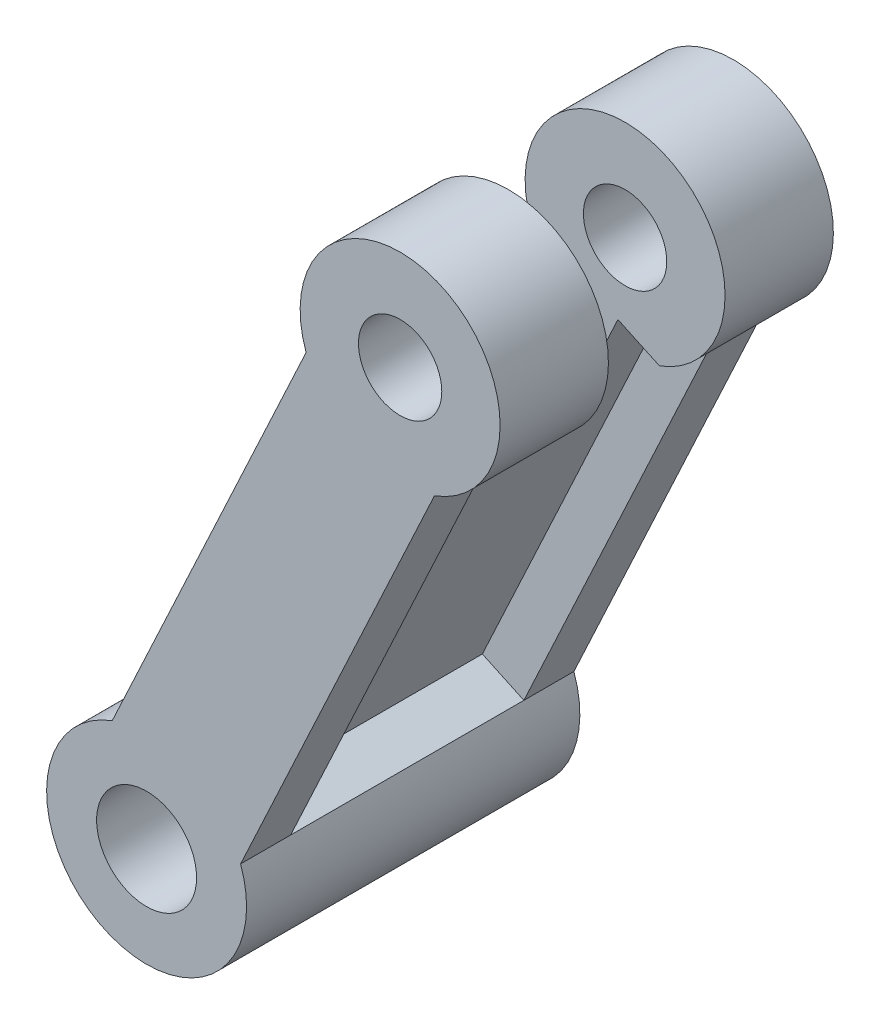
SolidWorks part; units mm, degrees
note: '?' marks a value the reader was unsure of.
material "Custom Plastic"
ref_plane "Piano frontale" through (0, 0, 0) normal (0, 0, 1) x (1, 0, 0)
ref_plane "Piano superiore" through (0, 0, 0) normal (0, 1, 0) x (1, 0, 0)
ref_plane "Piano destro" through (0, 0, 0) normal (1, 0, 0) x (0, 0, -1)
sketch "Sketch1" plane through (0, 0, 0) normal (0, 0, 1) x (1, 0, 0)
  line L0 (0, 0) -> (152.1426, 326.2708) construction
  line L1 (0, 0) -> (129.1028, 0) construction
  line L2 (95.7255, 305.8475) -> (-20.6191, 56.3458)
  line L3 (172.7616, 269.925) -> (56.4171, 20.4233)
  circle A0 centre (0, 0) radius 60
  circle A1 centre (152.1426, 326.2708) radius 60
  dimension "D1" = 120
  dimension "D2" = 120
  dimension "D3" = 65
  dimension "D4" = 360
  dimension "D5" = 42.5
extrude "Boss-Extrude1" add sketch "Sketch1" along normal mid plane 200 contours A1 L2 A0 L3 | A1 | A0
sketch "Sketch2" plane through (0, 0, 0) normal (0, 0, 1) x (1, 0, 0)
  circle A0 centre (0, 0) radius 30
  circle A1 centre (152.1426, 326.2708) radius 25
  dimension "D1" = 60
  dimension "D2" = 50
extrude "Cut-Extrude1" cut sketch "Sketch2" against normal through all and the other way through all
ref_plane "Plane1" through (0, 0, 120) normal (0, 0, 1) x (1, 0, 0)
ref_axis "Axis1" through (201.1363, 431.3382, 0) along (-0.4226, -0.9063, 0)?
ref_plane "Plane2" through (0, 0, 0) normal (-0.9063, 0.4226, 0) x (0, 0, 1)
sketch "Sketch9" plane through (0, 0, 0) normal (0, 0, 1) x (1, 0, 0)
  circle A0 centre (152.1426, 326.2708) radius 60
  dimension "D1" = 120
extrude "Cut-Extrude4" cut sketch "Sketch9" against normal mid plane 70
sketch "Sketch10" plane through (-38.5181, 17.9613, 0) normal (-0.9063, 0.4226, 0) x (0, 0, 1)
  line L0 (-35, 317.6473) -> (-35, 272.6473)
  line L1 (-25, 262.6473) -> (0, 262.6473)
  line L2 (35, 317.6473) -> (35, 272.6473)
  line L3 (25, 262.6473) -> (0, 262.6473)
  line L4 (-35, 317.6473) -> (35, 317.6473)
  arc A0 (35, 272.6473) -> (25, 262.6473) centre (25, 272.6473) cw
  arc A1 (-35, 272.6473) -> (-25, 262.6473) centre (-25, 272.6473) ccw
  point P9 (35, 262.6473)
  dimension "D2" = 10
  dimension "D1" = 55
extrude "Cut-Extrude5" cut sketch "Sketch10" against normal through all
sketch "Sketch12" plane through (-38.5181, 17.9613, 0) normal (-0.9063, 0.4226, 0) x (0, 0, 1)
  line L0 (-70, 317.6473) -> (70, 317.6473)
  line L1 (-35, 317.6473) -> (-100, 317.6473) construction
  line L2 (100, 317.6473) -> (35, 317.6473) construction
  line L3 (70, 317.6473) -> (70, 42.3527)
  line L4 (100, 42.3527) -> (-100, 42.3527) construction
  line L5 (70, 42.3527) -> (-70, 42.3527)
  line L6 (-70, 42.3527) -> (-70, 317.6473)
  line L7 (-100, 317.6473) -> (-100, 42.3527) construction
  line L8 (100, 317.6473) -> (100, 42.3527) construction
  dimension "D1" = 30
  dimension "D2" = 30
extrude "Cut-Extrude6" cut sketch "Sketch12" against normal blind 27.5
mirror "Mirror1" about plane through (0, 0, 0) normal (-0.9063, 0.4226, 0) of "Cut-Extrude6"
scale "Scale1" scale about centroid uniform scaling yes scale factor 0.1
